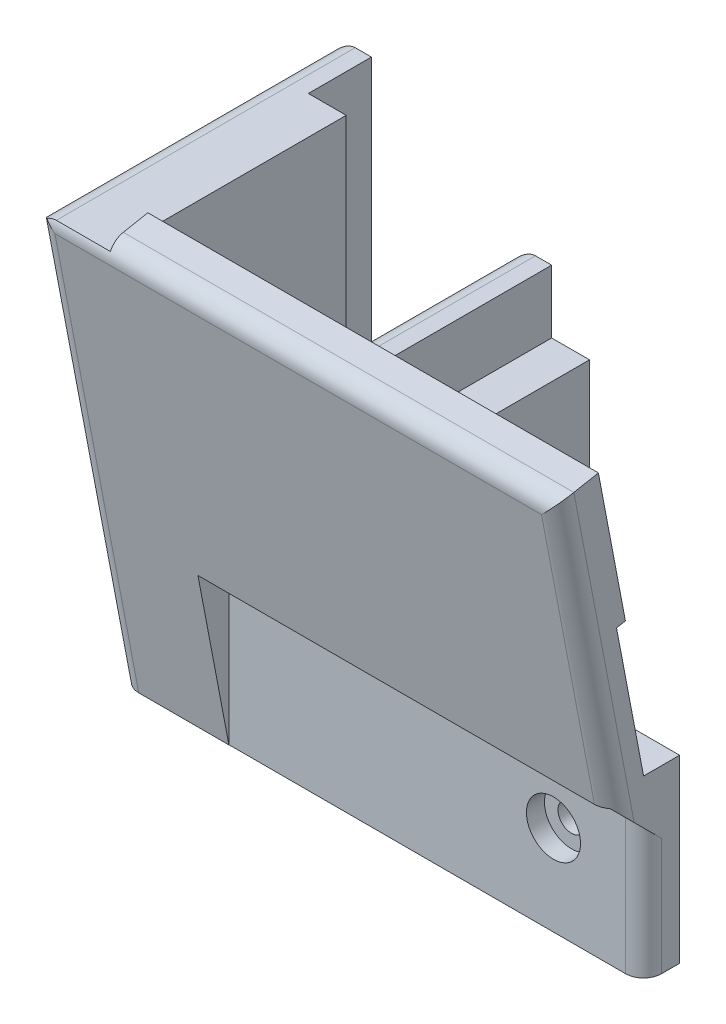
SolidWorks part; units mm, degrees
ref_plane "前视基准面" through (0, 0, 0) normal (0, 0, 1) x (1, 0, 0)
ref_plane "上视基准面" through (0, 0, 0) normal (0, 1, 0) x (1, 0, 0)
ref_plane "右视基准面" through (0, 0, 0) normal (1, 0, 0) x (0, 0, -1)
other "Configuration Table"
sketch "草图1" plane through (0, 0, 0) normal (1, 0, 0) x (0, 0, -1)
  line L0 (0, 0) -> (-10, 0)
  line L1 (-10, 0) -> (-17.6299, 40)
  line L2 (-17.6299, 40) -> (-10, 41.4554)
  line L3 (-10, 41.4554) -> (-4, 10)
  line L4 (-4, 10) -> (0, 10)
  line L5 (0, 10) -> (0, 0)
  dimension "D1" = 10
  dimension "D2" = 4
  dimension "D3" = 10
  dimension "D4" = 6
  dimension "D5" = 40
extrude "凸台-拉伸1" add sketch "草图1" along normal blind 50
sketch "草图2" plane through (0, 0, 0) normal (0, -1, 0) x (1, 0, 0)
  line L4 (0, 10) -> (0, 0)
  line L5 (0, 0) -> (50, 0)
  line L6 (50, 0) -> (50, 10)
  line L7 (50, 10) -> (0, 10)
  line L8 (0, 10) -> (0, 0)
  line L9 (0, 0) -> (50, 0)
  line L10 (50, 0) -> (50, 10)
  line L11 (50, 10) -> (0, 10)
  dimension "D1" = 0
extrude "凸台-拉伸2" add sketch "草图2" along normal blind 10
sketch "草图3" plane through (0, 0, 0) normal (-1, 0, 0) x (0, 0, 1)
  line L1 (0, 10) -> (10, 10)
  line L2 (0, 10) -> (0, -10)
  line L3 (0, -10) -> (10, -10)
  line L4 (10, 10) -> (10, -10)
extrude "凸台-拉伸3" add sketch "草图3" along normal blind 20
sketch "草图4" plane through (0, 10, 0) normal (0, 1, 0) x (1, 0, 0)
  line L1 (-20, 0) -> (0, 0)
  line L2 (-20, 0) -> (-20, -10)
  line L3 (-20, -10) -> (0, -10)
  line L4 (0, 0) -> (0, -10)
extrude "凸台-拉伸4" add sketch "草图4" along normal blind 30
sketch "草图5" plane through (50, 0, 0) normal (1, 0, 0) x (0, 0, -1)
  line L0 (-10, 10.004) -> (-11.9082, 10.004)
  line L1 (-17.6299, 40) -> (-10, 0) construction
  line L2 (-11.9082, 10.004) -> (-10, 0)
  line L3 (-10, 0) -> (-10, 10.004)
extrude "切除-拉伸1" cut sketch "草图5" against normal up to surface (50 mm away) up to face at (0, 32.2911, 11.4705)
chamfer "倒角1" distance 2 angle 45 1 edges at (25, 10.004, 10)
sketch "草图9" plane through (0, 0, 10) normal (0, 0, 1) x (1, 0, 0)
  line L0 (-20, 40) -> (-10, 40) construction
  line L1 (-20, 40) -> (0, 40) construction
  line L2 (-10, 40) -> (-10, 20) construction
  line L3 (50, -10) -> (50, 0) construction
  line L4 (50, -10) -> (50, 8.004) construction
  line L5 (50, 0) -> (40, 0) construction
  circle A0 centre (-10, 20) radius 1.5
  circle A1 centre (40, 0) radius 1.5
  dimension "D3" = 3
  dimension "D5" = 3
  dimension "D1" = 10
  dimension "D2" = 20
  dimension "D4" = 10
extrude "切除-拉伸2" cut sketch "草图9" against normal through all
sketch "草图12" plane through (0, 0, 10) normal (0, 0, 1) x (1, 0, 0)
  line L8 (0, 40) -> (-20, 40)
  line L9 (50, -10) -> (50, 8.004)
  line L10 (50, 8.004) -> (0, 8.004)
  line L11 (0, 8.004) -> (0, 40)
  line L15 (50, -10) -> (50, 8.004)
  line L16 (50, 8.004) -> (0, 8.004)
  line L17 (0, 8.004) -> (0, 40)
  line L19 (0, 40) -> (-20, 40)
  line L20 (-20, 40) -> (-20, -10)
  line L21 (-20, 40) -> (-20, -10)
  line L22 (-20, -10) -> (50, -10)
  line L23 (-20, -10) -> (50, -10)
  dimension "D1" = 0
extrude "切除-拉伸4" cut sketch "草图12" against normal blind 6
sketch "草图13" plane through (0, 8.004, 0) normal (0, -1, 0) x (1, 0, 0)
  line L0 (50, 4) -> (0, 4) construction
  line L1 (0, 10) -> (4, 10)
  line L2 (0, 10) -> (0, 4)
  line L3 (0, 4) -> (4, 4)
  line L4 (4, 10) -> (4, 4)
  line L6 (50, 10) -> (46, 10)
  line L7 (50, 10) -> (50, 4)
  line L8 (50, 4) -> (46, 4)
  line L9 (46, 10) -> (46, 4)
  dimension "D1" = 4
  dimension "D2" = 4
extrude "凸台-拉伸12" add sketch "草图13" along normal up to surface (18.004 mm away) up to face at (15, -10, 2)
fillet "圆角2" radius 2 3 edges at (25, 9.8906, 11.8866) (48, 8.004, 10) (2, 8.004, 10)
sketch "草图14" plane through (0, 0, 4) normal (0, 0, 1) x (1, 0, 0)
  line L0 (-20, -10) -> (0, -10) construction
  line L1 (-20, 40) -> (-4, 40)
  line L2 (-20, 40) -> (-20, -10)
  line L3 (-20, -10) -> (-4, -10)
  line L4 (-4, 40) -> (-4, -10)
  dimension "D1" = 16
extrude "切除-拉伸5" cut sketch "草图14" against normal blind 10
sketch "草图16" plane through (0, 0, 0) normal (1, 0, 0) x (0, 0, -1)
  line L0 (0, 10) -> (-4, 10)
  line L1 (-4, 10) -> (-5.9075, 20)
  line L2 (-4, 10) -> (-10, 41.4554) construction
  line L3 (-5.9075, 20) -> (0, 20)
  line L4 (0, 40) -> (0, 10) construction
  line L5 (0, 20) -> (0, 10)
  dimension "D1" = 10
extrude "凸台-拉伸14" add sketch "草图16" along normal blind 10
sketch "草图17" plane through (0, 0, 0) normal (0, 0, -1) x (-1, 0, 0)
  line L1 (0, 40) -> (4, 40)
  line L2 (0, 40) -> (0, -10)
  line L3 (0, -10) -> (4, -10)
  line L4 (4, 40) -> (4, -10)
extrude "凸台-拉伸15" add sketch "草图17" along normal blind 20
sketch "草图20" plane through (-4, 0, 0) normal (-1, 0, 0) x (0, 0, 1)
  line L0 (4, 20) -> (5.9075, 20) construction
  line L1 (4, 12) -> (-20, 12)
  line L2 (4, 12) -> (4, -10)
  line L3 (4, -10) -> (-20, -10)
  line L4 (-20, 12) -> (-20, -10)
  dimension "D1" = 8
extrude "切除-拉伸8" cut sketch "草图20" against normal up to surface (4 mm away) up to face at (0, 13.7188, 9.5514)
sketch "草图21" plane through (0, 0, 4) normal (0, 0, 1) x (1, 0, 0)
  line L5 (-4, 12) -> (0, 12)
  line L6 (0, 12) -> (0, 20)
  line L7 (0, 20) -> (0, 40)
  line L8 (0, 40) -> (-4, 40)
  line L9 (-4, 40) -> (-4, 12)
  line L10 (-4, 12) -> (0, 12)
  line L11 (0, 12) -> (0, 20)
  line L12 (0, 20) -> (0, 40)
  line L13 (0, 40) -> (-4, 40)
  line L14 (-4, 40) -> (-4, 12)
  dimension "D1" = 0
extrude "凸台-拉伸16" add sketch "草图21" along normal up to surface (13.6299 mm away) up to face at (25, 25.2475, 14.8159)
sketch "草图22" plane through (0, 12, 0) normal (0, -1, 0) x (1, 0, 0)
  line L1 (0, 0) -> (-4, 0)
  line L2 (0, 0) -> (0, 12.289)
  line L3 (0, 12.289) -> (-4, 12.289)
  line L4 (-4, 0) -> (-4, 12.289)
extrude "凸台-拉伸17" add sketch "草图22" along normal up to surface (22 mm away) up to face at (25, -10, 6)
sketch "草图23" plane through (0, 0, 0) normal (1, 0, 0) x (0, 0, -1)
  line L5 (-12.0019, 10.495) -> (-12.289, 12)
  line L6 (-12.289, 12) -> (-12.289, -10)
  line L7 (-12.289, -10) -> (-10, -10)
  line L8 (-10, -10) -> (-10, 7.1755)
  line L9 (-10.5858, 8.5898) -> (-11.4515, 9.4555)
  line L10 (-12.0019, 10.495) -> (-12.289, 12)
  line L11 (-12.289, 12) -> (-12.289, -10)
  line L12 (-12.289, -10) -> (-10, -10)
  line L13 (-10, -10) -> (-10, 7.1755)
  line L14 (-10.5858, 8.5898) -> (-11.4515, 9.4555)
  arc A2 (-12.0019, 10.495) -> (-11.4515, 9.4555) centre (-10.0373, 10.8697) ccw
  arc A3 (-10, 7.1755) -> (-10.5858, 8.5898) centre (-12, 7.1755) ccw
  arc A4 (-12.0019, 10.495) -> (-11.4515, 9.4555) centre (-10.0373, 10.8697) ccw
  arc A5 (-10, 7.1755) -> (-10.5858, 8.5898) centre (-12, 7.1755) ccw
  dimension "D1" = 0
extrude "切除-拉伸9" cut sketch "草图23" against normal up to surface (4 mm away) up to face at (-4, 13.7143, 0.3154)
sketch "草图24" plane through (46, 0, 0) normal (-1, 0, 0) x (0, 0, 1)
  line L5 (4, -10) -> (10, -10)
  line L6 (10, -10) -> (10, 7.1755)
  line L7 (10.5858, 8.5898) -> (10, 8.004)
  line L8 (10, 8.004) -> (4, 8.004)
  line L9 (4, 8.004) -> (4, -10)
  line L10 (4, -10) -> (10, -10)
  line L11 (10, -10) -> (10, 7.1755)
  line L12 (10.5858, 8.5898) -> (10, 8.004)
  line L13 (10, 8.004) -> (4, 8.004)
  line L14 (4, 8.004) -> (4, -10)
  arc A1 (10.5858, 8.5898) -> (10, 7.1755) centre (12, 7.1755) ccw
  arc A2 (10.5858, 8.5898) -> (10, 7.1755) centre (12, 7.1755) ccw
  dimension "D1" = 0
extrude "切除-拉伸10" cut sketch "草图24" against normal up to surface (4 mm away) up to face at (50, 11.7188, 8.5607)
sketch "草图25" plane through (0, 0, 4) normal (0, 0, 1) x (1, 0, 0)
  circle A0 centre (40, 0) radius 3
  dimension "D1" = 6
extrude "切除-拉伸11" cut sketch "草图25" against normal offset from surface (2 mm away) 2 up to face at (41.5, 0, 0)
sketch "草图26" plane through (10, 0, 0) normal (1, 0, 0) x (0, 0, -1)
  line L4 (0, 10) -> (0, 20)
  line L5 (0, 20) -> (-5.9075, 20)
  line L6 (-5.9075, 20) -> (-4, 10)
  line L7 (-4, 10) -> (0, 10)
  line L8 (0, 10) -> (0, 20)
  line L9 (0, 20) -> (-5.9075, 20)
  line L10 (-5.9075, 20) -> (-4, 10)
  line L11 (-4, 10) -> (0, 10)
  dimension "D1" = 0
extrude "切除-拉伸12" cut sketch "草图26" against normal blind 10
sketch "草图27" plane through (-4, 0, 0) normal (-1, 0, 0) x (0, 0, 1)
  line L0 (-20, 40) -> (-20, 12)
  line L1 (-20, 12) -> (-20, 40) construction
  line L8 (0, -10) -> (10, -10)
  line L9 (10, -10) -> (10, 7.1755)
  line L10 (10.5858, 8.5898) -> (11.4515, 9.4555)
  line L11 (12.0019, 10.495) -> (17.6299, 40)
  line L12 (17.6299, 40) -> (-20, 40)
  line L13 (-20, 40) -> (-20, 12)
  line L14 (-20, 12) -> (0, 12)
  line L15 (0, 12) -> (0, -10)
  line L16 (0, -10) -> (10, -10)
  line L17 (10, -10) -> (10, 7.1755)
  line L18 (10.5858, 8.5898) -> (11.4515, 9.4555)
  line L19 (12.0019, 10.495) -> (17.6299, 40)
  line L20 (17.6299, 40) -> (-20, 40)
  line L22 (-20, 12) -> (0, 12)
  line L23 (0, 12) -> (0, -10)
  arc A2 (10.5858, 8.5898) -> (10, 7.1755) centre (12, 7.1755) ccw
  arc A3 (11.4515, 9.4555) -> (12.0019, 10.495) centre (10.0373, 10.8697) ccw
  arc A4 (10.5858, 8.5898) -> (10, 7.1755) centre (12, 7.1755) ccw
  arc A5 (11.4515, 9.4555) -> (12.0019, 10.495) centre (10.0373, 10.8697) ccw
  dimension "D2" = 0
  dimension "D1" = 0
extrude "凸台-拉伸19" add sketch "草图27" along normal blind 4
sketch "草图34" plane through (0, 12, 0) normal (0, -1, 0) x (1, 0, 0)
  line L4 (0, 0) -> (-8, 0)
  line L5 (-8, 0) -> (-8, -20)
  line L6 (-8, -20) -> (0, -20)
  line L7 (0, -20) -> (0, 0)
  line L8 (0, 0) -> (-8, 0)
  line L9 (-8, 0) -> (-8, -20)
  line L10 (-8, -20) -> (0, -20)
  line L11 (0, -20) -> (0, 0)
  dimension "D1" = 0
extrude "凸台-拉伸21" add sketch "草图34" along normal up to surface (22 mm away) up to face at (15.3333, -10, 4.6667)
sketch "草图35" plane through (0, 0, -20) normal (0, 0, -1) x (-1, 0, 0)
  line L0 (0, -10) -> (0, 10) construction
  line L1 (8, -10) -> (0, -10)
  line L2 (8, -10) -> (8, 10)
  line L3 (8, 10) -> (0, 10)
  line L4 (0, -10) -> (0, 10)
  dimension "D1" = 20
extrude "凸台-拉伸22" add sketch "草图35" along normal blind 20
sketch "草图28" plane through (0, 0, 0) normal (1, 0, 0) x (0, 0, -1)
  line L1 (20, 40) -> (13, 40)
  line L2 (20, 40) -> (20, 10)
  line L3 (20, 3) -> (13, 3)
  line L4 (13, 40) -> (13, 3)
  line L5 (40, 10) -> (20, 10) construction
  line L6 (40, 10) -> (40, -10) construction
  line L7 (20, 3) -> (40, 3)
  line L9 (20, 10) -> (40, 10)
  line L10 (40, 3) -> (40, 10)
  dimension "D1" = 7
  dimension "D2" = 7
extrude "切除-拉伸18" cut sketch "草图28" against normal blind 4.2
sketch "草图38" plane through (-8, 0, 0) normal (-1, 0, 0) x (0, 0, 1)
  line L0 (-40, 0) -> (-30, 0) construction
  line L1 (-40, -10) -> (-40, 10) construction
  circle A0 centre (-30, 0) radius 1.5
  dimension "D2" = 3
  dimension "D1" = 10
extrude "切除-拉伸19" cut sketch "草图38" against normal through all
sketch "草图39" plane through (-8, 0, 0) normal (-1, 0, 0) x (0, 0, 1)
  circle A0 centre (-30, 0) radius 2.9
  dimension "D1" = 5.8
extrude "切除-拉伸20" cut sketch "草图39" against normal offset from surface (6 mm away) 2 up to face at (0, 0, -28.5)
sketch "草图42" plane through (0, -0.3851, 2.0191) normal (0, 0.1874, -0.9823) x (-1, 0, 0)
  line L0 (-50, 10.5724) -> (-50, 42.5949) construction
  line L1 (-50, 26.5836) -> (0, 26.5836)
  line L2 (-50, 26.5836) -> (-50, 42.5949)
  line L3 (-50, 42.5949) -> (0, 42.5949)
  line L4 (0, 26.5836) -> (0, 42.5949)
extrude "凸台-拉伸23" add sketch "草图42" along normal blind 1
sketch "草图44" plane through (0, -1.8405, 9.6489) normal (0, -0.1874, 0.9823) x (1, 0, 0)
  line L5 (0, 42.5949) -> (-8, 42.5949)
  line L6 (-8, 42.5949) -> (-8, 12.5579)
  line L7 (-8, 12.5579) -> (50, 12.5579)
  line L8 (50, 12.5579) -> (50, 42.5949)
  line L9 (50, 42.5949) -> (0, 42.5949)
  line L10 (0, 42.5949) -> (-8, 42.5949)
  line L11 (-8, 42.5949) -> (-8, 12.5579)
  line L12 (-8, 12.5579) -> (50, 12.5579)
  line L13 (50, 12.5579) -> (50, 42.5949)
  line L14 (50, 42.5949) -> (0, 42.5949)
  dimension "D1" = 0
extrude "切除-拉伸21" cut sketch "草图44" against normal blind 4
sketch "草图45" plane through (0, 12.3355, 2.3529) normal (0, 0.9823, 0.1874) x (1, 0, 0)
  line L2 (-8, -9.8229) -> (-8, -11.6966)
  line L3 (-8, -11.6966) -> (4, -11.6966)
  line L4 (-8, -9.8229) -> (50, -9.8229)
  line L5 (50, -9.8229) -> (50, -5.8229)
  line L6 (50, -5.8229) -> (-8, -5.8229)
  line L7 (-8, -5.8229) -> (-8, -9.8229)
  line L8 (4, -9.8229) -> (50, -9.8229)
  line L9 (50, -9.8229) -> (50, -5.8229)
  line L10 (50, -5.8229) -> (-8, -5.8229)
  line L11 (-8, -5.8229) -> (-8, -9.8229)
  line L12 (4, -9.8229) -> (4, -11.6966)
  dimension "D1" = 0
extrude "切除-拉伸22" cut sketch "草图45" against normal blind 44
chamfer "倒角2" distance 3 angle 45 1 edges at (27, 8.004, 4)
fillet "圆角3" radius 2 8 edges at (50, -2.498, 4) (-8, 40, -3.2211) (-8, 25, -20) (-8, 10, -30) (-8, 0, -40) (25, 40.7495, 13.7007) (50, 24.3767, 10.5777) (-8, 15, 8.7891)
